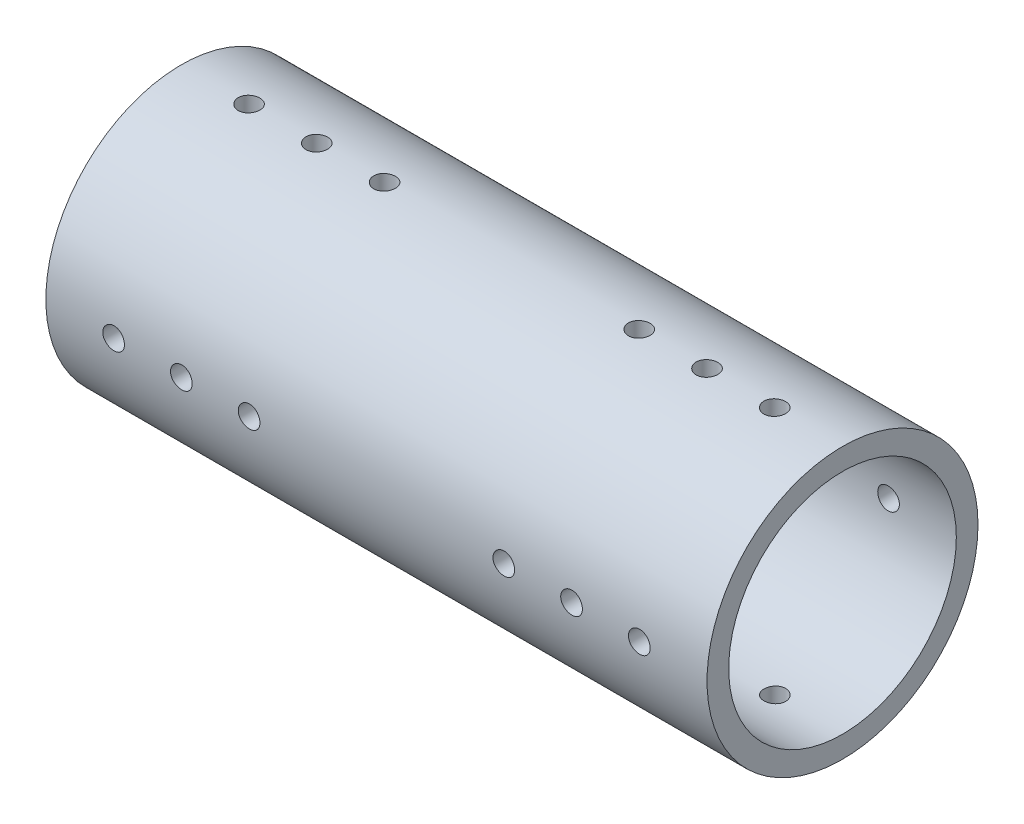
SolidWorks part; units mm, degrees
material "Zoltek Panex 33"
ref_plane "Спереди" through (0, 0, 0) normal (0, 0, 1) x (1, 0, 0)
ref_plane "Сверху" through (0, 0, 0) normal (0, 1, 0) x (1, 0, 0)
ref_plane "Справа" through (0, 0, 0) normal (1, 0, 0) x (0, 0, -1)
other "Configuration Table"
sketch "Эскиз2" plane through (0, 0, 0) normal (1, 0, 0) x (0, 0, -1)
  circle A0 centre (0, 0) radius 25
  circle A1 centre (0, 0) radius 21
  dimension "D1" = 50
  dimension "D2" = 42
extrude "Бобышка-Вытянуть2" add sketch "Эскиз2" along normal blind 122
ref_plane "Плоскость1" through (0, 0, 25) normal (0, 0, 1) x (1, 0, 0)
sketch "Эскиз4" plane through (0, 0, 25) normal (0, 0, 1) x (1, 0, 0)
  line L0 (0, -25) -> (122, -25) construction
  line L1 (122, -25) -> (122, 25) construction
  circle A0 centre (12.5, 0) radius 2
  circle A1 centre (109.5, 0) radius 2
  circle A2 centre (25, 0) radius 2
  circle A3 centre (37.5, 0) radius 2
  circle A4 centre (97, 0) radius 2
  circle A5 centre (84.5, 0) radius 2
  dimension "D1" = 4
  dimension "D4" = 4
  dimension "D6" = 4
  dimension "D8" = 4
  dimension "D10" = 4
  dimension "D11" = 4
  dimension "D2" = 12.5
  dimension "D3" = 25
  dimension "D5" = 12.5
  dimension "D7" = 12.5
  dimension "D9" = 12.5
  dimension "15" = 12.5
  dimension "D12" = 12.5
extrude "Вырез-Вытянуть2" cut sketch "Эскиз4" against normal through all and the other way blind 10 contours A0 | A1 | A2 | A3 | A5 | A4
pattern_circular "Круговой массив1" count 4 over 360 about axis through (122, 0, 0) along (-1, 0, 0) of "Вырез-Вытянуть2"
equation "\"Diameter\"= 50мм"
equation "\"D1@Эскиз2\"= \"Diameter\""
equation "\"Length\"= 122мм"
equation "\"Thickness\"= 4мм"
equation "\"D1@Бобышка-Вытянуть2\"= \"Length\""
equation "\"D2@Эскиз2\" = \"Diameter\" - \"Thickness\" * 2"
equation "\"D4@Эскиз4\"=\"D1@Эскиз4\""
equation "\"D5@Эскиз4\"=\"D2@Эскиз4\""
equation "\"D3@Эскиз4\"=\"Diameter\"/2"
equation "\"D6@Эскиз4\"=\"D1@Эскиз4\""
equation "\"D8@Эскиз4\"=\"D6@Эскиз4\""
equation "\"D10@Эскиз4\"=\"D4@Эскиз4\""
equation "\"D11@Эскиз4\"=\"D4@Эскиз4\""
equation "\"D9@Эскиз4\"=\"D7@Эскиз4\""
